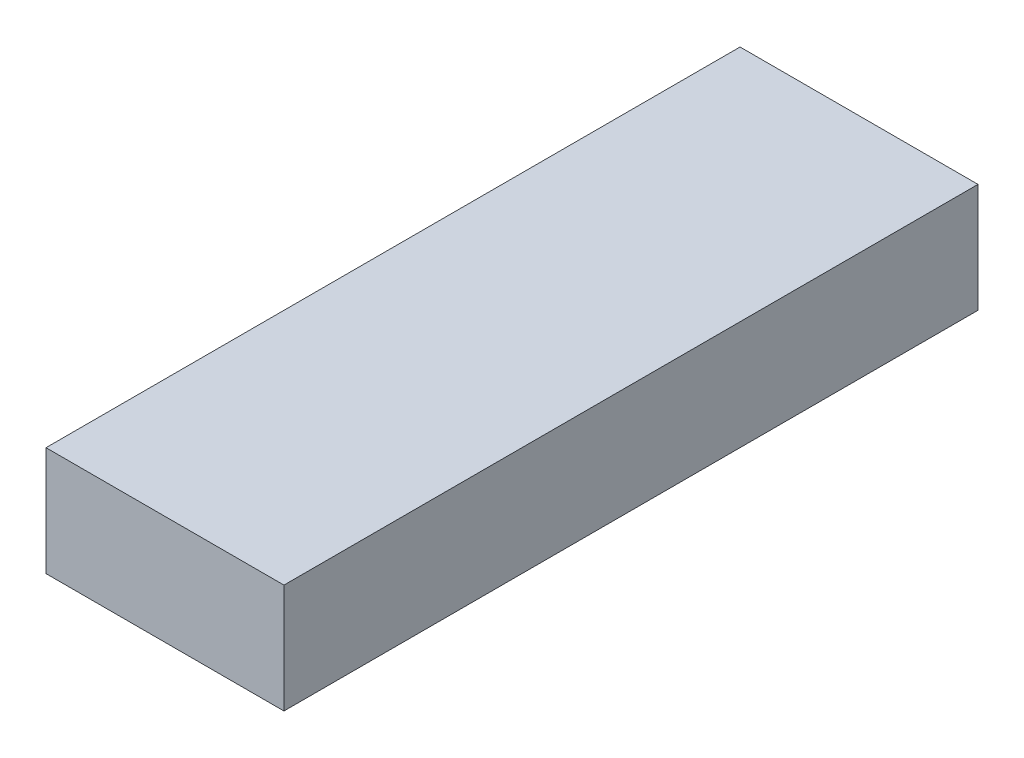
SolidWorks part; units mm, degrees
ref_plane "Front Plane" through (0, 0, 0) normal (0, 0, 1) x (1, 0, 0)
ref_plane "Top Plane" through (0, 0, 0) normal (0, 1, 0) x (1, 0, 0)
ref_plane "Right Plane" through (0, 0, 0) normal (1, 0, 0) x (0, 0, -1)
sketch "Sketch1" plane through (0, 0, 0) normal (0, 0, 1) x (1, 0, 0)
  line L1 (-24, -11) -> (24, -11)
  line L2 (-24, -11) -> (-24, 11)
  line L3 (-24, 11) -> (24, 11)
  line L4 (24, -11) -> (24, 11)
  line L5 (-24, -11) -> (24, 11) construction
  line L6 (-24, 11) -> (24, -11) construction
  point P0 (0, 0)
  dimension "D1" = 22
  dimension "D2" = 47.9999
extrude "Boss-Extrude1" add sketch "Sketch1" along normal mid plane 139.9997
equation "\"D2@Sketch1\"=\"Batt X@Quad Assemb.sldasm\""
equation "\"D1@Sketch1\"=\"Batt Z@Quad Assemb.sldasm\""
equation "\"D1@Boss-Extrude1\"=\"Batt Y@Quad Assemb.sldasm\""
